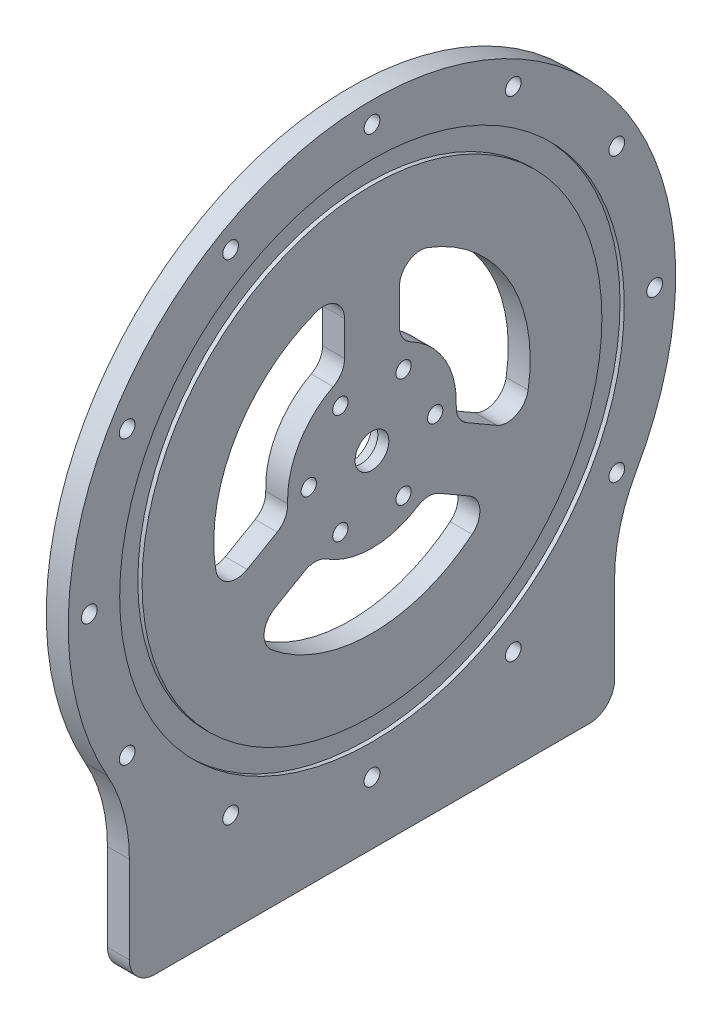
SolidWorks part; units mm, degrees
material "6061 Alloy"
ref_plane "Front Plane" through (0, 0, 0) normal (0, 0, 1) x (1, 0, 0)
ref_plane "Top Plane" through (0, 0, 0) normal (0, 1, 0) x (1, 0, 0)
ref_plane "Right Plane" through (0, 0, 0) normal (1, 0, 0) x (0, 0, -1)
sketch "Sketch1" plane through (0, 0, 0) normal (1, 0, 0) x (0, 0, -1)
  line L0 (0, -1000) -> (0, 49000) construction
  line L1 (5.5562, 0) -> (2.7781, 4.8119) construction
  line L2 (2.7781, 4.8119) -> (-2.7781, 4.8119) construction
  line L3 (-2.7781, 4.8119) -> (-5.5562, 0) construction
  line L4 (-5.5562, 0) -> (-2.7781, -4.8119) construction
  line L5 (-2.7781, -4.8119) -> (2.7781, -4.8119) construction
  line L6 (2.7781, -4.8119) -> (5.5562, 0) construction
  line L7 (-65.405, -103.8551) -> (65.405, -103.8551)
  line L8 (-73.025, -96.2351) -> (-73.025, -69.997)
  line L10 (73.025, -96.2351) -> (73.025, -69.997)
  circle A0 centre (0, 0) radius 69.85 construction
  circle A1 centre (0, 0) radius 76.2 construction
  circle A2 centre (0, 0) radius 5.08
  circle A3 centre (0, 0) radius 3.9688 construction
  arc A4 (79.6018, -44.9981) -> (-79.6018, -44.9981) centre (0, 0) ccw
  circle A5 centre (0, 0) radius 11.5094 construction
  circle A6 centre (0, 0) radius 91.44 construction
  arc A7 (65.405, -103.8551) -> (73.025, -96.2351) centre (65.405, -96.2351) ccw
  arc A8 (-65.405, -103.8551) -> (-73.025, -96.2351) centre (-65.405, -96.2351) cw
  arc A9 (79.6018, -44.9981) -> (73.025, -69.997) centre (123.825, -69.997) ccw
  arc A10 (-73.025, -69.997) -> (-79.6018, -44.9981) centre (-123.825, -69.997) ccw
  point P19 (73.025, -103.8551)
  point P26 (-73.025, -103.8551)
  dimension "D1" = 152.4
  dimension "D2" = 139.7
  dimension "D3" = 10.16
  dimension "D4" = 7.9375
  dimension "D5" = 15.24
  dimension "D6" = 23.0188
  dimension "D8" = 7.62
  dimension "D9" = 50.8
  dimension "D7" = 146.05
extrude "Boss-Extrude1" add sketch "Sketch1" along normal blind 6.604
sketch "Sketch2" plane through (0, 0, 0) normal (1, 0, 0) x (0, 0, -1)
  circle A0 centre (0, 0) radius 6.35 construction
  circle A1 centre (0, 0) radius 6.477
  dimension "D1" = 12.7
  dimension "D2" = 12.954
extrude "Cut-Extrude1" cut sketch "Sketch2" along direction (1, 0, 0) on the side of the normal blind 3.302
sketch "Sketch3" plane through (6.604, 0, 0) normal (1, 0, 0) x (0, 0, -1)
  circle A0 centre (0, 0) radius 75.946
  circle A1 centre (0, 0) radius 69.215
  dimension "D2" = 138.43
  dimension "D1" = 6.731
extrude "Cut-Extrude2" cut sketch "Sketch3" against normal blind 1.27
sketch "Sketch4" plane through (0, 0, 0) normal (-1, 0, 0) x (0, 0, 1)
  line L0 (0, -1000) -> (0, 49000) construction
  line L1 (-1000, 0) -> (49000, 0) construction
  circle A1 centre (0, 85.09) radius 2.3812
  circle A3 centre (0, 0) radius 85.09 construction
  circle A4 centre (42.545, 73.6901) radius 2.3812
  circle A5 centre (73.6901, 42.545) radius 2.3813
  circle A6 centre (85.09, 0) radius 2.3813
  circle A7 centre (73.6901, -42.545) radius 2.3813
  circle A8 centre (42.545, -73.6901) radius 2.3812
  circle A9 centre (0, -85.09) radius 2.3812
  circle A10 centre (-42.545, -73.6901) radius 2.3812
  circle A11 centre (-73.6901, -42.545) radius 2.3813
  circle A12 centre (-85.09, 0) radius 2.3813
  circle A13 centre (-73.6901, 42.545) radius 2.3813
  circle A14 centre (-42.545, 73.6901) radius 2.3812
  point P34 (0, 0)
  dimension "D2" = 12
extrude "Cut-Extrude3" cut sketch "Sketch4" against normal through all
sketch "Sketch5" plane through (0, 0, 0) normal (-1, 0, 0) x (0, 0, 1)
  circle A0 centre (0, 85.09) radius 3.7783
  circle A3 centre (42.545, 73.6901) radius 3.7783
  circle A5 centre (-42.545, 73.6901) radius 3.7783
  circle A6 centre (73.6901, 42.545) radius 3.7783
  circle A7 centre (85.09, 0) radius 3.7783
  circle A8 centre (73.6901, -42.545) radius 3.7783
  circle A9 centre (42.545, -73.6901) radius 3.7783
  circle A10 centre (0, -85.09) radius 3.7783
  circle A11 centre (-42.545, -73.6901) radius 3.7783
  circle A12 centre (-73.6901, -42.545) radius 3.7783
  circle A13 centre (-85.09, 0) radius 3.7783
  circle A14 centre (-73.6901, 42.545) radius 3.7783
  point P29 (0, 0)
  dimension "D1" = 12
extrude "Cut-Extrude4" cut sketch "Sketch5" against normal blind 1.27
sketch "Sketch6" plane through (0, 0, 0) normal (-1, 0, 0) x (0, 0, 1)
  line L0 (-1000, 0) -> (49000, 0) construction
  line L1 (0, 0) -> (25000, 43301.2702) construction
  line L2 (0, 0) -> (25000, -43301.2702) construction
  circle A0 centre (0, 0) radius 25.4 construction
  circle A1 centre (-19.0117, 0) radius 2.3813
  circle A2 centre (-9.5059, 16.4647) radius 2.3813
  circle A3 centre (9.5059, 16.4647) radius 2.3812
  circle A4 centre (19.0117, 0) radius 2.3813
  circle A5 centre (9.5059, -16.4647) radius 2.3813
  circle A6 centre (-9.5059, -16.4647) radius 2.3813
  point P19 (0, 0)
  dimension "D1" = 6
  dimension "D2" = 50.8
  dimension "D3" = 4.7625
  dimension "D4" = 19.0117
hole_wizard "#12-28 Tapped Hole1" positions "Sketch8" profile "Sketch7" tap size "#12-28" standard "ANSI Inch" end condition through all
sketch "Sketch8" plane through (0, -19.7442, 32.4273) normal (-1, 0, 0) x (0, 0, 1)
  point P0 (-41.9332, 36.2089)
  point P3 (-22.9214, 36.2089)
  point P6 (-13.4156, 19.7442)
  point P9 (-22.9214, 3.2796)
  point P12 (-41.9332, 3.2796)
  point P15 (-51.4391, 19.7442)
sketch "Sketch7" plane through (0, 16.4647, -9.5059) normal (0, 1, 0) x (0, 0, 1)
  line L0 (0, 0) -> (0, 6.604)
  line L1 (0, 6.604) -> (2.3114, 6.604)
  line L2 (2.3114, 6.604) -> (2.3114, 0)
  line L5 (2.3114, 0) -> (0, 0)
  line L11 (0, -6.35) -> (0, 107.95) construction
  dimension "Thru Tap Drill Dia." = 4.6228
  dimension "Thru Tap Drill Depth" = 6.604
cosmetic thread "Hole Thread1"
cosmetic thread "Hole Thread2"
cosmetic thread "Hole Thread3"
cosmetic thread "Hole Thread4"
cosmetic thread "Hole Thread5"
cosmetic thread "Hole Thread6"
sketch "Sketch9" plane through (0, 0, 0) normal (-1, 0, 0) x (0, 0, 1)
  line L0 (0, 0) -> (0, 138.31) construction
  line L1 (0, 0) -> (103.2188, -59.5934) construction
  line L2 (0, 0) -> (-103.0172, -59.477) construction
  line L5 (-8.255, 38.6047) -> (-8.255, 28.1914)
  line L7 (8.255, 38.6047) -> (8.255, 28.1914)
  line L8 (37.5601, -12.1533) -> (28.542, -6.9467)
  line L10 (29.3051, -26.4514) -> (20.287, -21.2448)
  line L12 (-29.3051, -26.4514) -> (-20.287, -21.2448)
  line L14 (-37.5601, -12.1533) -> (-28.542, -6.9467)
  arc A0 (-8.255, 24.0211) -> (-24.9304, -4.8615) centre (0, 0) ccw construction
  arc A1 (-16.8519, 44.5438) -> (-47.0021, -7.6777) centre (0, 0) ccw
  arc A2 (-11.684, 22.5531) -> (-25.3736, -1.1579) centre (0, 0) ccw
  arc A3 (24.9304, -4.8615) -> (8.255, 24.0211) centre (0, 0) ccw construction
  arc A4 (25.3736, -1.1579) -> (11.684, 22.5531) centre (0, 0) ccw
  arc A5 (47.0021, -7.6777) -> (16.8519, 44.5438) centre (0, 0) ccw
  arc A6 (-16.6754, -19.1596) -> (16.6754, -19.1596) centre (0, 0) ccw construction
  arc A7 (-13.6896, -21.3952) -> (13.6896, -21.3952) centre (0, 0) ccw
  arc A8 (-30.1501, -36.8661) -> (30.1501, -36.8661) centre (0, 0) ccw
  arc A9 (-16.8519, 44.5438) -> (-8.255, 38.6047) centre (-14.605, 38.6047) cw
  arc A10 (-8.255, 28.1914) -> (-11.684, 22.5531) centre (-14.605, 28.1914) cw
  arc A11 (-25.3736, -1.1579) -> (-28.542, -6.9467) centre (-31.717, -1.4474) cw
  arc A12 (-47.0021, -7.6777) -> (-37.5601, -12.1533) centre (-40.7351, -6.654) ccw
  arc A13 (-30.1501, -36.8661) -> (-29.3051, -26.4514) centre (-26.1301, -31.9506) cw
  arc A14 (-20.287, -21.2448) -> (-13.6896, -21.3952) centre (-17.112, -26.744) cw
  arc A15 (13.6896, -21.3952) -> (20.287, -21.2448) centre (17.112, -26.744) cw
  arc A16 (30.1501, -36.8661) -> (29.3051, -26.4514) centre (26.1301, -31.9506) ccw
  arc A17 (47.0021, -7.6777) -> (37.5601, -12.1533) centre (40.7351, -6.654) cw
  arc A18 (28.542, -6.9467) -> (25.3736, -1.1579) centre (31.717, -1.4474) cw
  arc A19 (16.8519, 44.5438) -> (8.255, 38.6047) centre (14.605, 38.6047) ccw
  arc A20 (11.684, 22.5531) -> (8.255, 28.1914) centre (14.605, 28.1914) cw
  point P24 (0, 0)
  dimension "D1" = 120
  dimension "D3" = 95.25
  dimension "D4" = 50.8
  dimension "D7" = 6.35
  dimension "D2" = 120
  dimension "D5" = 16.51
  dimension "D6" = 3
extrude "Cut-Extrude5" cut sketch "Sketch9" against normal through all
